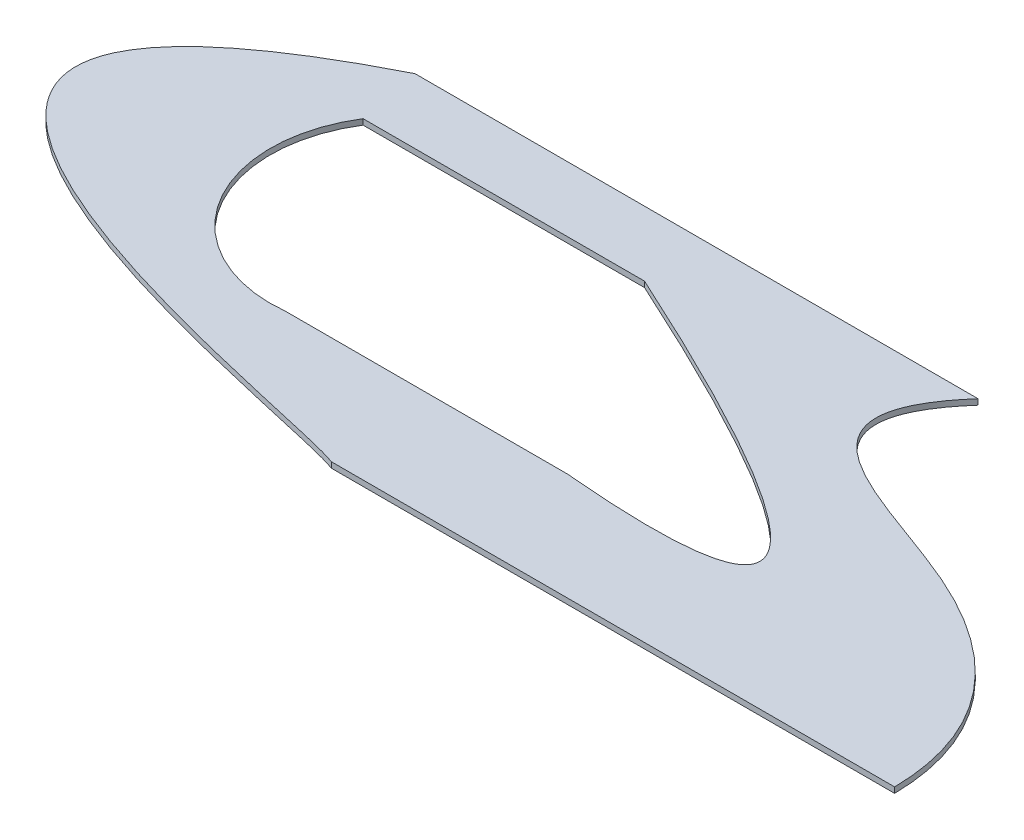
SolidWorks part; units mm, degrees
ref_plane "Front Plane" through (0, 0, 0) normal (0, 0, 1) x (1, 0, 0)
ref_plane "Top Plane" through (0, 0, 0) normal (0, 1, 0) x (1, 0, 0)
ref_plane "Right Plane" through (0, 0, 0) normal (1, 0, 0) x (0, 0, -1)
sketch "Sketch1" plane through (0, 0, 0) normal (0, 1, 0) x (1, 0, 0)
  line L0 (47.7774, 66.6799) -> (97.7774, 66.6799)
  line L1 (75, 47.6087) -> (175, 47.6087)
  line L2 (25, 103.1967) -> (75, 103.1967)
  line L3 (22.6849, 114.7312) -> (122.6849, 114.7312)
  arc A0 (25, 103.1967) -> (47.7774, 66.6799) centre (45.2056, 90.4378) ccw
  spline S0 degree 3 poles (122.6849, 114.7312) (104.7714, 94.3303) (153.3058, 88.7243) (174.7825, 64.1932) (175, 47.6087) knots 0 0 0 0 0.52399 1 1 1 1
  spline S1 degree 2 poles (75, 103.1967) (168.7084, 60.2938) (97.7774, 66.6799) knots 0 0 0 1 1 1
  spline S2 degree 3 poles (22.6849, 114.7312) (-65.9907, 70.2268) (60.8905, 52.7673) (75, 47.6087) knots 0 0 0 0 1 1 1 1
  point P14 (126.0153, 67.4946)
  point P16 (75, 47.6087)
  dimension "D5" = 100
  dimension "D1" = 100
  dimension "D2" = 50
  dimension "D3" = 100
  dimension "D4" = 50
extrude "Boss-Extrude1" add sketch "Sketch1" along normal blind 1
